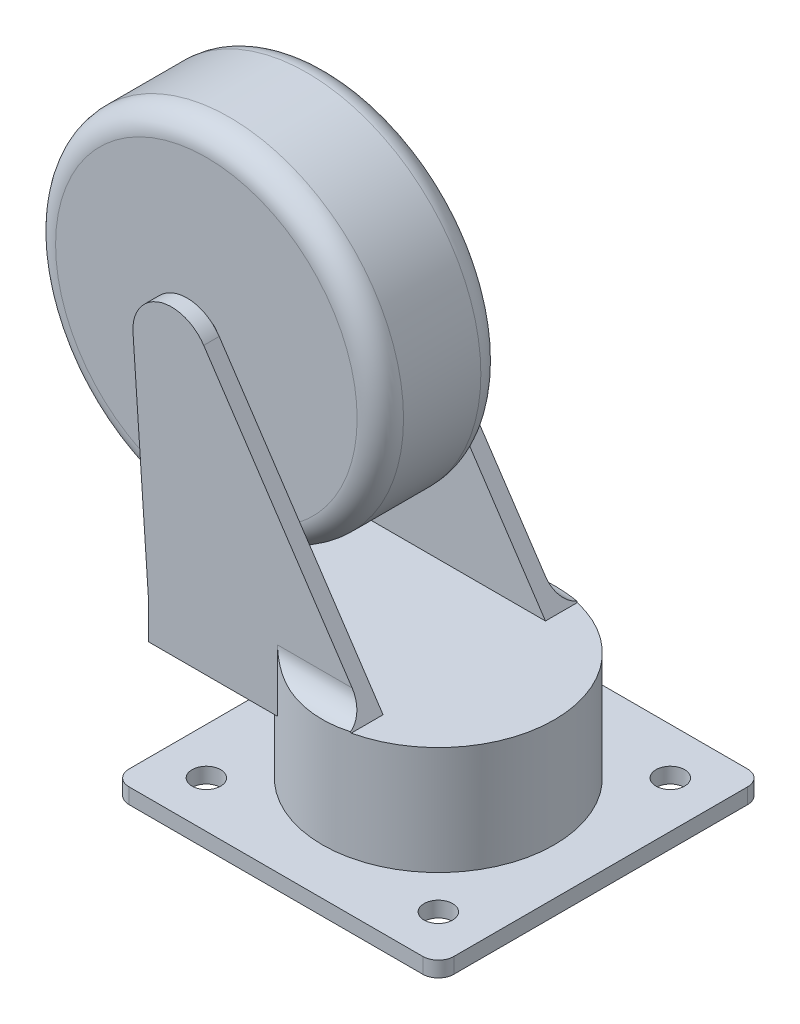
SolidWorks part; units mm, degrees
ref_plane "Front Plane" through (0, 0, 0) normal (0, 0, 1) x (1, 0, 0)
ref_plane "Top Plane" through (0, 0, 0) normal (0, 1, 0) x (1, 0, 0)
ref_plane "Right Plane" through (0, 0, 0) normal (1, 0, 0) x (0, 0, -1)
sketch "Sketch1" plane through (0, 0, 0) normal (0, 1, 0) x (1, 0, 0)
  line L0 (0, 21) -> (0, -21) construction
  line L1 (-19, 21) -> (19, 21)
  line L2 (-21, 19) -> (-21, -19)
  line L3 (-19, -21) -> (19, -21)
  line L4 (21, 19) -> (21, -19)
  line L5 (-21, 21) -> (21, -21) construction
  line L6 (-21, -21) -> (21, 21) construction
  line L7 (-21, 0) -> (21, 0) construction
  circle A0 centre (-15, 15) radius 1.851
  circle A2 centre (15, 15) radius 1.851
  circle A3 centre (15, -15) radius 1.851
  circle A4 centre (-15, -15) radius 1.851
  arc A5 (-21, -19) -> (-19, -21) centre (-19, -19) ccw
  arc A6 (19, -21) -> (21, -19) centre (19, -19) ccw
  arc A7 (19, 21) -> (21, 19) centre (19, 19) cw
  arc A8 (-19, 21) -> (-21, 19) centre (-19, 19) ccw
  point P0 (0, 0)
  dimension "D4" = 2
  dimension "D1" = 42
  dimension "D2" = 42
  dimension "D3" = 30
extrude "Boss-Extrude1" add sketch "Sketch1" along normal blind 2
sketch "Sketch2" plane through (0, 2, 0) normal (0, 1, 0) x (1, 0, 0)
  circle A0 centre (0, 0) radius 15
  dimension "D1" = 30
extrude "Boss-Extrude2" add sketch "Sketch2" along normal blind 9
sketch "Sketch3" plane through (0, 11, 0) normal (0, 1, 0) x (1, 0, 0)
  line L0 (0, 0) -> (-36.9933, 0) construction
  line L1 (-25, 12.5) -> (-8.2916, 12.5)
  line L2 (-25, -12.5) -> (-8.2916, -12.5)
  line L3 (-25, 12.5) -> (-25, -12.5)
  circle A0 centre (0, 0) radius 15 construction
  circle A1 centre (0, 0) radius 15 construction
  arc A2 (-8.2916, -12.5) -> (-8.2916, 12.5) centre (0, 0) ccw
  dimension "D1" = 25
  dimension "D2" = 25
extrude "Boss-Extrude3" add sketch "Sketch3" along normal blind 5
sketch "Sketch4" plane through (0, 0, 12.5) normal (0, 0, 1) x (1, 0, 0)
  line L0 (0, 0) -> (0, 48.0736) construction
  line L1 (0, 45) -> (-39.2355, 45) construction
  line L2 (-19, 0) -> (19, 0) construction
  line L3 (-25, 16) -> (-26.988, 44.6539)
  line L4 (3.3542, 16) -> (-17.8405, 47.7746)
  line L5 (15, 16) -> (-8.2916, 16) construction
  line L6 (-25, 16) -> (3.3542, 16)
  circle A0 centre (-22, 45) radius 1.5
  arc A1 (-17.8405, 47.7746) -> (-26.988, 44.6539) centre (-22, 45) ccw
  dimension "D3" = 3
  dimension "D4" = 10
  dimension "D1" = 45
  dimension "D2" = 22
extrude "Boss-Extrude4" add sketch "Sketch4" against normal blind 2
mirror "Mirror1" about plane through (0, 0, 0) normal (0, 0, 1) of "Boss-Extrude4"
fillet "Fillet1" radius 3 2 edges at (-2.4687, 16, -12.5) (-2.4687, 16, 12.5)
sketch "Sketch5" plane through (0, 0, 0) normal (0, 0, 1) x (1, 0, 0)
  circle A0 centre (-22, 45) radius 22.5
  dimension "D1" = 45
extrude "Boss-Extrude5" add sketch "Sketch5" along normal blind 8 and the other way blind 8 separate body
fillet "Fillet2" radius 3 2 edges at (0.5, 45, 8) (0.5, 45, -8)
sketch "Sketch6" plane through (0, 0, 12.5) normal (0, 0, 1) x (1, 0, 0)
  circle A0 centre (-22, 45) radius 1.5
extrude "Boss-Extrude6" add sketch "Sketch6" against normal up to surface (25 mm away) up to face at (-15.8941, 24.5638, -12.5)
